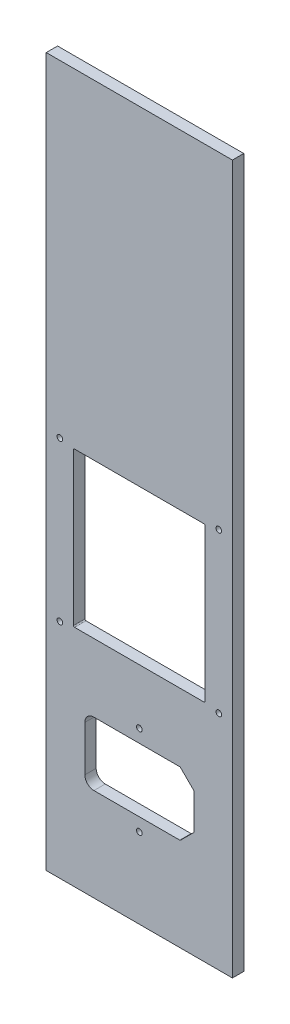
SolidWorks part; units mm, degrees
ref_plane "Front Plane" through (0, 0, 0) normal (0, 0, 1) x (1, 0, 0)
ref_plane "Top Plane" through (0, 0, 0) normal (0, 1, 0) x (1, 0, 0)
ref_plane "Right Plane" through (0, 0, 0) normal (1, 0, 0) x (0, 0, -1)
sketch "Sketch1" plane through (0, 0, 0) normal (0, 0, 1) x (1, 0, 0)
  line L1 (-41, -156) -> (41, -156)
  line L2 (-41, -156) -> (-41, 156)
  line L3 (-41, 156) -> (41, 156)
  line L4 (41, -156) -> (41, 156)
  line L5 (-41, -156) -> (41, 156) construction
  line L6 (-41, 156) -> (41, -156) construction
  point P0 (0, 0)
  dimension "D1" = 312
  dimension "D2" = 82
extrude "Boss-Extrude1" add sketch "Sketch1" along normal blind 5
sketch "Sketch2" plane through (0, 0, 5) normal (0, 0, 1) x (1, 0, 0)
  line L0 (0, -1000) -> (0, 49000) construction
  line L1 (-24, -115) -> (24, -115)
  line L2 (-24, -115) -> (-24, -87)
  line L3 (-24, -87) -> (24, -87)
  line L4 (24, -115) -> (24, -87)
  line L5 (-24, -115) -> (24, -87) construction
  line L6 (-24, -87) -> (24, -115) construction
  line L7 (-41, -156) -> (41, -156) construction
  circle A0 centre (0, -81.25) radius 1.25
  circle A1 centre (0, -120.75) radius 1.25
  point P0 (0, -101)
  dimension "D6" = 2.5
  dimension "D7" = 2.5
  dimension "D1" = 28
  dimension "D2" = 48
  dimension "D3" = 55
  dimension "D4" = 19.75
  dimension "D5" = 19.75
extrude "Cut-Extrude1" cut sketch "Sketch2" against normal blind 10
chamfer "Chamfer1" distance 6 angle 45 2 edges at (24, -115, 2.5) (24, -87, 2.5)
fillet "Fillet1" radius 4 2 edges at (-24, -115, 2.5) (-24, -87, 2.5)
sketch "Sketch3" plane through (0, 0, 5) normal (0, 0, 1) x (1, 0, 0)
  line L0 (0, -1000) -> (0, 49000) construction
  line L1 (18, -87) -> (-20, -87) construction
  line L2 (-29, -57) -> (29, -57)
  line L3 (-29, -57) -> (-29, 11)
  line L4 (-29, 11) -> (29, 11)
  line L5 (29, -57) -> (29, 11)
  line L6 (-29, -57) -> (29, 11) construction
  line L7 (-29, 11) -> (29, -57) construction
  point P1 (0, -23)
  dimension "D1" = 58
  dimension "D2" = 68
  dimension "D3" = 30
extrude "Cut-Extrude2" cut sketch "Sketch3" against normal through all
hole_wizard "M3x0.5 Tapped Hole1" positions "Sketch7" profile "Sketch6" tap size "M3x0.5" standard "ANSI Metric" end condition through all
sketch "Sketch7" plane through (0, 0, 5) normal (0, 0, 1) x (1, 0, 0)
  line L0 (0, -23) -> (0, -57) construction
  line L1 (-29, -23) -> (29, -23) construction
  line L2 (-29, -57) -> (29, -57) construction
  line L3 (-29, 11) -> (-29, -57) construction
  point P7 (-35, 12)
  point P8 (35, 12)
  point P9 (35, -58)
  point P10 (-35, -58)
  dimension "D1" = 35
  dimension "D2" = 35
  dimension "D3" = 35
  dimension "D4" = 35
  dimension "D5" = 35
  dimension "D6" = 35
  dimension "D7" = 35
  dimension "D8" = 35
sketch "Sketch6" plane through (-35, 12, 5) normal (1, 0, 0) x (0, -1, 0)
  line L0 (0, 0) -> (0, 5)
  line L1 (0, 5) -> (1.25, 5)
  line L2 (1.25, 5) -> (1.25, 0)
  line L5 (1.25, 0) -> (0, 0)
  line L11 (0, -6.35) -> (0, 107.95) construction
  dimension "Thru Tap Drill Dia." = 2.5
  dimension "Thru Tap Drill Depth" = 5
cosmetic thread "Hole Thread1" parameters "D2"=3
cosmetic thread "Hole Thread2" parameters "D2"=3
cosmetic thread "Hole Thread3" parameters "D2"=3
cosmetic thread "Hole Thread4" parameters "D2"=3
fillet "Fillet2" radius 0.5 8 edges at (18, -115, 2.5) (24, -109, 2.5) (24, -93, 2.5) (18, -87, 2.5) (29, -57, 2.5) (-29, -57, 2.5) (-29, 11, 2.5) (29, 11, 2.5)
